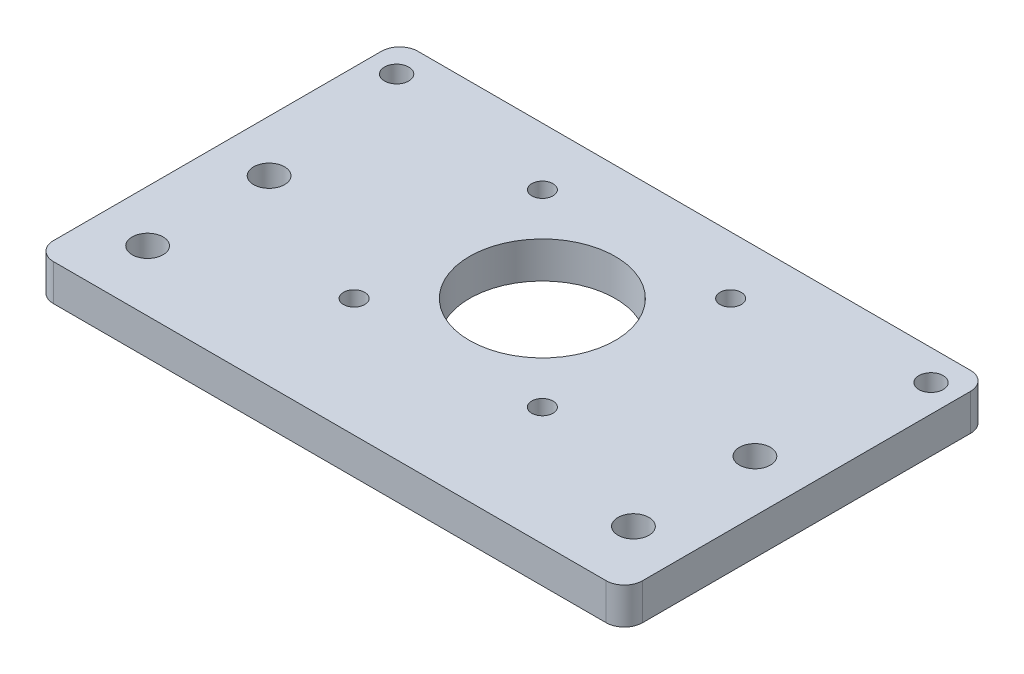
SolidWorks part; units mm, degrees
material "Acrylic (Medium-high impact)"
ref_plane "Front Plane" through (0, 0, 0) normal (0, 0, 1) x (1, 0, 0)
ref_plane "Top Plane" through (0, 0, 0) normal (0, 1, 0) x (1, 0, 0)
ref_plane "Right Plane" through (0, 0, 0) normal (1, 0, 0) x (0, 0, -1)
sketch "Sketch1" plane through (0, 0, 0) normal (0, 1, 0) x (1, 0, 0)
  line L1 (48.5, -30) -> (-48.5, -30)
  line L2 (48.5, -30) -> (48.5, 30)
  line L3 (48.5, 30) -> (-48.5, 30)
  line L4 (-48.5, -30) -> (-48.5, 30)
  line L5 (48.5, -30) -> (-48.5, 30) construction
  line L6 (48.5, 30) -> (-48.5, -30) construction
  point P0 (0, 0)
  dimension "D1" = 97
  dimension "D2" = 60
extrude "Base" add sketch "Sketch1" along normal blind 6
sketch "Sketch2" plane through (0, 6, 0) normal (0, 1, 0) x (1, 0, 0)
  line L0 (48.5, 30) -> (-48.5, 30) construction
  line L1 (0, 5) -> (0, 17.5) construction
  circle A0 centre (-15.5, 20.5) radius 1.75
  circle A1 centre (15.5, 20.5) radius 1.75
  circle A2 centre (0, 5) radius 12
  circle A3 centre (-15.5, -10.5) radius 1.75
  circle A4 centre (15.5, -10.5) radius 1.75
  dimension "D1" = 24
  dimension "D2" = 3.5
  dimension "D5" = 25
  dimension "D3" = 31
  dimension "D4" = 31
  dimension "D6" = 15.5
extrude "StepperHoles" cut sketch "Sketch2" against normal through all
fillet "FilletEdges3mm" radius 3 4 edges at (48.5, 3, 30) (48.5, 3, -30) (-48.5, 3, -30) (-48.5, 3, 30)
sketch "Sketch3" plane through (0, 0, 0) normal (0, -1, 0) x (1, 0, 0)
  line L0 (-45.5, 30) -> (45.5, 30) construction
  line L1 (0, 0) -> (0, 12.8623) construction
  circle A0 centre (-40, 20) radius 2.55
  circle A1 centre (-40, 0) radius 2.55
  circle A2 centre (40, 20) radius 2.55
  circle A3 centre (40, 0) radius 2.55
  dimension "D1" = 5.1
  dimension "D2" = 10
  dimension "D3" = 80
  dimension "D4" = 20
extrude "HolesForCorners" cut sketch "Sketch3" against normal through all
sketch "Sketch5" plane through (0, 0, 0) normal (0, -1, 0) x (1, 0, 0)
  line L1 (0, 0) -> (0, -5.988) construction
  line L2 (45.5, -30) -> (-45.5, -30) construction
  circle A0 centre (-44, -25) radius 2
  circle A1 centre (44, -25) radius 2
  dimension "D1" = 4
  dimension "D2" = 88
  dimension "D3" = 5
extrude "CableTieHoles" cut sketch "Sketch5" against normal through all
equation "\"D6@Sketch2\"=\"D4@Sketch2\"/2"
